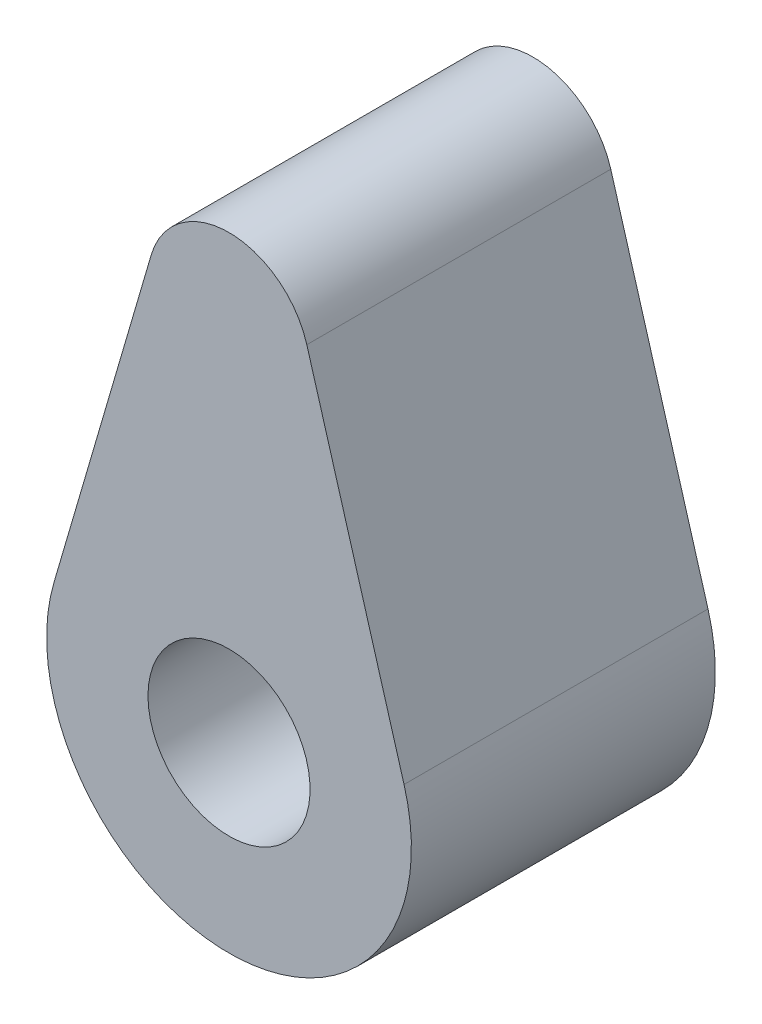
SolidWorks part; units mm, degrees
ref_plane "Спереди" through (0, 0, 0) normal (0, 0, 1) x (1, 0, 0)
ref_plane "Сверху" through (0, 0, 0) normal (0, 1, 0) x (1, 0, 0)
ref_plane "Справа" through (0, 0, 0) normal (1, 0, 0) x (0, 0, -1)
sketch "Эскиз1" plane through (0, 0, 0) normal (0, 0, 1) x (1, 0, 0)
  line L0 (0, 17.8) -> (0, 0) construction
  line L1 (-3.8389, 18.9236) -> (-8.6376, 2.5281)
  line L2 (3.8389, 18.9236) -> (8.6376, 2.5281)
  circle A0 centre (0, 0) radius 9
  circle A1 centre (0, 17.8) radius 4
  dimension "D2" = 18
  dimension "D3" = 8
  dimension "D1" = 17.8
extrude "Бобышка-Вытянуть1" add sketch "Эскиз1" along normal blind 15 contours A1 | L0 A1 L1 A0 | A1 L0 A0 L2 | A0 region at (3.6581, 11.1302, 0) region at (-3.6581, 11.1302, 0) region at (-3.1106, 15.4693, 0) region at (5.244, 6.9988, 0)
sketch "Эскиз2" plane through (0, 0, 0) normal (0, 0, -1) x (-1, 0, 0)
  line L0 (0, 17.8) -> (0, 0) construction
  line L1 (-2.6, 17.8) -> (-4.7378, 4.3028)
  line L2 (2.6, 17.8) -> (4.7378, 4.3028)
  circle A0 centre (0, 0) radius 6.4
  circle A1 centre (0, 17.8) radius 2.6
  circle A2 centre (0, 0) radius 4
  dimension "D2" = 12.8
  dimension "D3" = 5.2
  dimension "D4" = 8
  dimension "D1" = 18
extrude "Вырез-Вытянуть1" cut sketch "Эскиз2" against normal blind 4 contours L0 A1 L1 A0 | A1 | A1 L0 A0 L2 | A0 region at (-2.0093, 10.4655, 0) region at (2.0093, 10.4655, 0) region at (1.7865, 16.0135, 0) region at (-2.5173, 5.6867, 0)
extrude "Вырез-Вытянуть2" cut sketch "Эскиз2<3>" against normal through all contours A2 region at (0, 0, 0)
sketch "Эскиз2<3>" plane through (0, 0, 0) normal (0, 0, -1) x (-1, 0, 0) same geometry as "Эскиз2"
sketch "Эскиз3" plane through (0, 0, 0) normal (0, 1, 0) x (1, 0, 0)
  line L0 (0, 0) -> (0, -35.0948) construction
